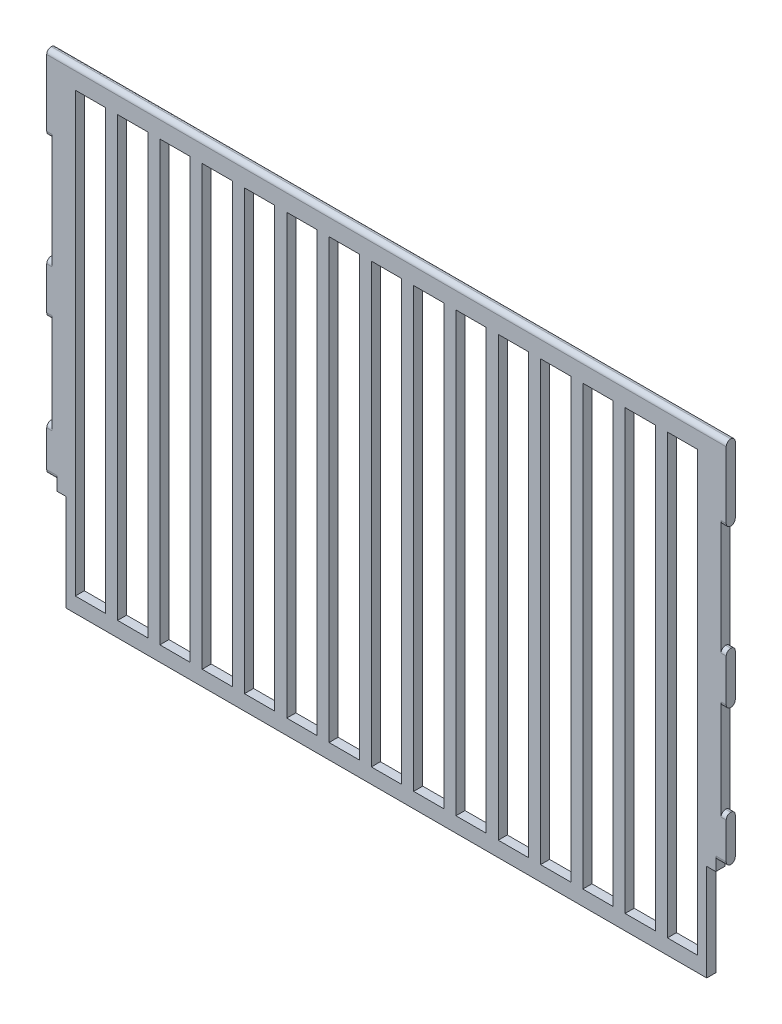
SolidWorks part; units mm, degrees
ref_plane "前视基准面" through (0, 0, 0) normal (0, 0, 1) x (1, 0, 0)
ref_plane "上视基准面" through (0, 0, 0) normal (0, 1, 0) x (1, 0, 0)
ref_plane "右视基准面" through (0, 0, 0) normal (1, 0, 0) x (0, 0, -1)
sketch "草图1" plane through (0, 0, 0) normal (0, 0, 1) x (1, 0, 0)
  line L0 (124.75, 71) -> (-96.75, 71)
  line L1 (110.75, 71) -> (-110.75, 71)
  line L2 (110.75, 46) -> (110.75, 11)
  line L4 (-110.75, 46) -> (-110.75, 11)
  line L5 (0, -88) -> (0, 71) construction
  line L6 (110.75, 0) -> (-110.75, 0) construction
  line L7 (5, -81) -> (-5, -81)
  line L8 (5, -81) -> (5, 64)
  line L9 (5, 64) -> (-5, 64)
  line L10 (-5, -81) -> (-5, 64)
  line L11 (0, 64) -> (0, -81) construction
  line L12 (5, -8.5) -> (-5, -8.5) construction
  line L13 (19, -81) -> (19, 64)
  line L14 (9, -81) -> (9, 64)
  line L15 (19, 64) -> (9, 64)
  line L16 (19, -81) -> (9, -81)
  line L17 (138.75, 71) -> (-82.75, 71)
  line L18 (33, -81) -> (33, 64)
  line L19 (23, -81) -> (23, 64)
  line L20 (33, 64) -> (23, 64)
  line L21 (33, -81) -> (23, -81)
  line L22 (152.75, 71) -> (-68.75, 71)
  line L23 (47, -81) -> (47, 64)
  line L24 (37, -81) -> (37, 64)
  line L25 (47, 64) -> (37, 64)
  line L26 (47, -81) -> (37, -81)
  line L27 (166.75, 71) -> (-54.75, 71)
  line L28 (61, -81) -> (61, 64)
  line L29 (51, -81) -> (51, 64)
  line L30 (61, 64) -> (51, 64)
  line L31 (61, -81) -> (51, -81)
  line L32 (180.75, 71) -> (-40.75, 71)
  line L33 (75, -81) -> (75, 64)
  line L34 (65, -81) -> (65, 64)
  line L35 (75, 64) -> (65, 64)
  line L36 (75, -81) -> (65, -81)
  line L37 (194.75, 71) -> (-26.75, 71)
  line L38 (89, -81) -> (89, 64)
  line L39 (79, -81) -> (79, 64)
  line L40 (89, 64) -> (79, 64)
  line L41 (89, -81) -> (79, -81)
  line L42 (208.75, 71) -> (-12.75, 71)
  line L43 (103, -81) -> (103, 64)
  line L44 (93, -81) -> (93, 64)
  line L45 (103, 64) -> (93, 64)
  line L46 (103, -81) -> (93, -81)
  line L47 (-9, -81) -> (-9, 64)
  line L48 (-9, -81) -> (-19, -81)
  line L49 (-19, -81) -> (-19, 64)
  line L50 (-9, 64) -> (-19, 64)
  line L51 (-23, -81) -> (-23, 64)
  line L52 (-23, -81) -> (-33, -81)
  line L53 (-33, -81) -> (-33, 64)
  line L54 (-23, 64) -> (-33, 64)
  line L55 (-37, -81) -> (-37, 64)
  line L56 (-37, -81) -> (-47, -81)
  line L57 (-47, -81) -> (-47, 64)
  line L58 (-37, 64) -> (-47, 64)
  line L59 (-51, -81) -> (-51, 64)
  line L60 (-51, -81) -> (-61, -81)
  line L61 (-61, -81) -> (-61, 64)
  line L62 (-51, 64) -> (-61, 64)
  line L63 (-65, -81) -> (-65, 64)
  line L64 (-65, -81) -> (-75, -81)
  line L65 (-75, -81) -> (-75, 64)
  line L66 (-65, 64) -> (-75, 64)
  line L67 (-79, -81) -> (-79, 64)
  line L68 (-79, -81) -> (-89, -81)
  line L69 (-89, -81) -> (-89, 64)
  line L70 (-79, 64) -> (-89, 64)
  line L71 (-93, -81) -> (-93, 64)
  line L72 (-93, -81) -> (-103, -81)
  line L73 (-103, -81) -> (-103, 64)
  line L74 (-93, 64) -> (-103, 64)
  line L76 (-110.75, 71) -> (-112.45, 71)
  line L78 (-110.75, 46) -> (-112.45, 46)
  line L79 (-112.45, 71) -> (-112.45, 46)
  line L80 (-110.75, 71) -> (-112.45, 46) construction
  line L81 (-110.75, 46) -> (-112.45, 71) construction
  line L82 (-110.75, 11) -> (-112.45, 11)
  line L84 (-110.75, -6) -> (-112.45, -6)
  line L85 (-112.45, 11) -> (-112.45, -6)
  line L86 (-110.75, 11) -> (-112.45, -6) construction
  line L87 (-110.75, -6) -> (-112.45, 11) construction
  line L88 (-110.75, -36) -> (-112.45, -36)
  line L91 (-112.45, -36) -> (-112.45, -51)
  line L92 (-112.0838, -43.5391) -> (-112.45, -51) construction
  line L93 (-110.75, -71) -> (-112.45, -36) construction
  line L94 (112.45, -36) -> (112.45, -51)
  line L95 (110.75, -36) -> (112.45, -36)
  line L97 (110.75, -6) -> (112.45, -6)
  line L98 (112.45, 11) -> (112.45, -6)
  line L99 (110.75, 11) -> (112.45, 11)
  line L101 (110.75, 46) -> (112.45, 46)
  line L102 (112.45, 71) -> (112.45, 46)
  line L103 (110.75, 71) -> (112.45, 71)
  line L105 (110.75, -6) -> (110.75, -36)
  line L106 (-110.75, -6) -> (-110.75, -36)
  line L107 (-112.45, -51) -> (-109, -51)
  line L108 (-109, -51) -> (-109, -54)
  line L109 (112.45, -51) -> (109, -51)
  line L110 (109, -51) -> (109, -54)
  line L111 (109, -54) -> (106, -54)
  line L114 (-109, -54) -> (-106, -54)
  line L115 (-106, -71) -> (-106, -54)
  line L116 (-106, -86) -> (106, -86)
  line L117 (106, -86) -> (106, -71)
  line L118 (106, -71) -> (106, -54)
  line L123 (-106, -71) -> (-106, -86)
  point P0 (0, 0)
  point P4 (0, -8.5)
  point P81 (-111.6, 58.5)
  point P86 (-111.6, 2.5)
  point P90 (-112.0838, -43.5391)
  point P91 (-111.6, -36)
  point P114 (-109.25, -62.5)
  point P121 (-1.1852, -78.5)
  dimension "D1" = 221.5
  dimension "D2" = 142
  dimension "D3" = 145
  dimension "D4" = 10
  dimension "D7" = 1.7
  dimension "D8" = 1.7
  dimension "D9" = 1.7
  dimension "D10" = 15
  dimension "D11" = 17
  dimension "D12" = 30
  dimension "D13" = 25
  dimension "D14" = 35
  dimension "D15" = 3
  dimension "D16" = 17
  dimension "D17" = 15
  dimension "D18" = 212
  dimension "D5" = 8
  dimension "D6" = 8
extrude "凸台-拉伸1" add sketch "草图1" along normal blind 3 contours L106 L88 L91 L94 L95 L105 L97 L98 L99 L2 L101 L102 L42 L0 L37 L32 L27 L22 L17 L1 L76 L79 L78 L4 L82 L85 L84 L43 L46 L44 L45 L38 L41 L39 L40 L33 L36 L34 L35 L28 L31 region at (109.7072, 58.5, 0)
fillet "圆角1" radius 1.5 22 edges at (111.6, -6, 3) (111.6, -6, 0) (110.725, -51, 0) (110.725, -51, 3) (111.6, -36, 0) (111.6, -36, 3) (111.6, 11, 3) (111.6, 11, 0) (111.6, 46, 0) (111.6, 46, 3) (0, 71, 0) (0, 71, 3) (-111.6, 11, 0) (-111.6, 11, 3) (-111.6, -6, 0) (-111.6, -6, 3) (-111.6, 46, 0) (-111.6, 46, 3) (-111.6, -36, 0) (-111.6, -36, 3) (-110.725, -51, 0) (-110.725, -51, 3)
